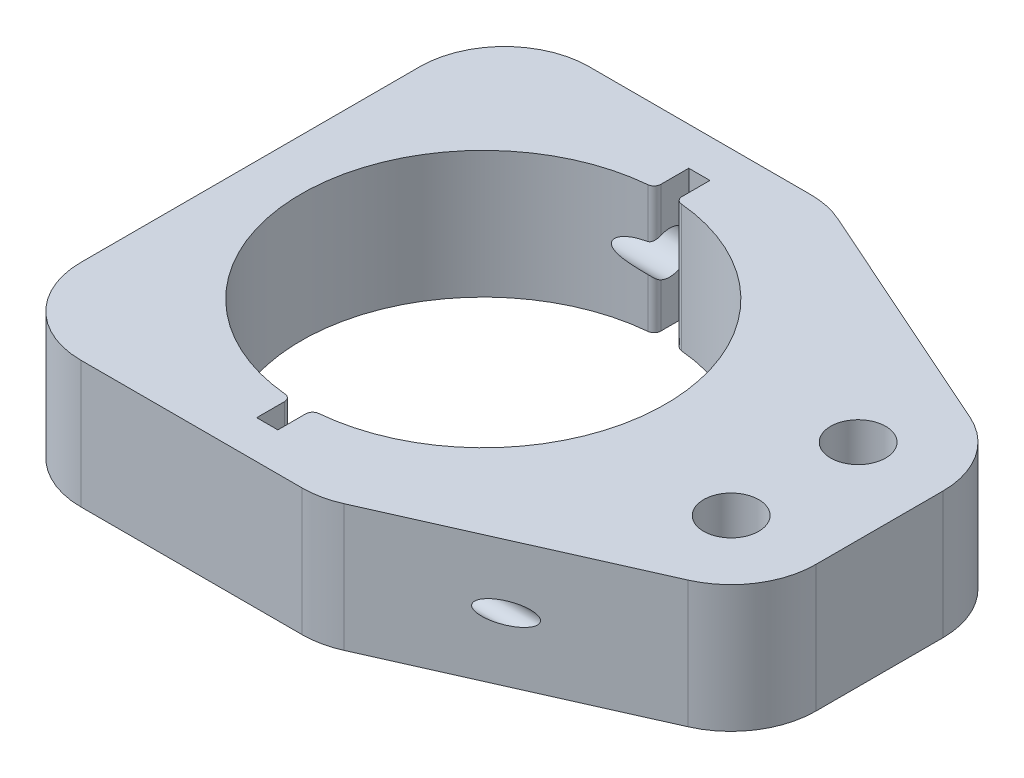
SolidWorks part; units mm, degrees
material "PET"
ref_plane "Front Plane" through (0, 0, 0) normal (0, 0, 1) x (1, 0, 0)
ref_plane "Top Plane" through (0, 0, 0) normal (0, 1, 0) x (1, 0, 0)
ref_plane "Right Plane" through (0, 0, 0) normal (1, 0, 0) x (0, 0, -1)
sketch "Sketch1" plane through (0, 0, 0) normal (0, 1, 0) x (1, 0, 0)
  line L0 (0, 0) -> (-27.5, 0) construction
  line L1 (46.75, 30) -> (-27.5, 30)
  line L2 (46.75, 30) -> (46.75, -30)
  line L3 (46.75, -30) -> (-27.5, -30)
  line L4 (-27.5, 30) -> (-27.5, -30)
  line L5 (-1.25, 21.4636) -> (-1.25, 25.5)
  line L6 (1.25, -25.5) -> (-1.25, -25.5)
  line L7 (1.25, -25.5) -> (1.25, -21.4636)
  line L8 (1.25, 25.5) -> (-1.25, 25.5)
  line L9 (-1.25, -25.5) -> (-1.25, -21.4636)
  line L10 (1.25, -25.5) -> (-1.25, 25.5) construction
  line L11 (1.25, 25.5) -> (-1.25, -25.5) construction
  line L12 (1.25, 21.4636) -> (1.25, 25.5)
  line L13 (36.75, -7.493) -> (36.75, 7.493) construction
  line L14 (36.75, 0) -> (46.75, 0) construction
  arc A0 (-1.25, 21.4636) -> (-1.25, -21.4636) centre (0, 0) ccw
  arc A1 (1.25, -21.4636) -> (1.25, 21.4636) centre (0, 0) ccw
  circle A2 centre (36.75, 7.493) radius 3.25
  circle A3 centre (36.75, -7.493) radius 3.25
  point P7 (-21.5, 0)
  point P10 (-27.5, 0)
  point P23 (21.5, 0)
  point P24 (33.5, 7.493)
  dimension "D1" = 43
  dimension "D6" = 6.5
  dimension "D2" = 6
  dimension "D3" = 60
  dimension "D4" = 51
  dimension "D5" = 2.5
  dimension "D7" = 14.986
  dimension "D8" = 10
  dimension "D9" = 12
extrude "Boss-Extrude1" add sketch "Sketch1" along normal blind 15
sketch "Sketch2" plane through (-27.5, 0, 0) normal (-1, 0, 0) x (0, 0, 1)
  line L0 (-23.25, 7.5) -> (23.25, 7.5) construction
  line L1 (0, 7.5) -> (0, 0) construction
  line L2 (0, 7.5) -> (0, 15) construction
  line L3 (-30, 15) -> (30, 15) construction
  circle A0 centre (-23.25, 7.5) radius 1.25
  circle A1 centre (23.25, 7.5) radius 1.25
  dimension "D1" = 2.5
  dimension "D2" = 46.5
extrude "Cut-Extrude1" cut sketch "Sketch2" against normal through all
sketch "Sketch3" plane through (-27.5, 0, 0) normal (-1, 0, 0) x (0, 0, 1)
  circle A0 centre (-23.25, 7.5) radius 2.5
  circle A1 centre (23.25, 7.5) radius 2.5
  dimension "D1" = 5
extrude "Cut-Extrude2" cut sketch "Sketch3" against normal up to surface (26.25 mm away) up to face at (-1.25, 7.5, -24.5)
sketch "Sketch4" plane through (0, 15, 0) normal (0, 1, 0) x (1, 0, 0)
  line L0 (10.75, -30) -> (46.75, -14)
  line L1 (-27.5, -30) -> (46.75, -30) construction
  line L2 (46.75, -30) -> (46.75, 30) construction
  line L3 (46.75, -14) -> (46.75, -30)
  line L4 (46.75, -30) -> (10.75, -30)
  dimension "D1" = 16
  dimension "D2" = 36
extrude "Cut-Extrude3" cut sketch "Sketch4" against normal through all
mirror "Mirror1" about plane through (0, 0, 0) normal (0, 0, 1) of "Cut-Extrude3"
fillet "Fillet1" radius 10 6 edges at (-27.5, 7.5, -30) (-27.5, 7.5, 30) (46.75, 7.5, 14) (46.75, 7.5, -14) (10.75, 7.5, -30) (10.75, 7.5, 30)
fillet "Fillet2" radius 0.8 6 edges at (1.25, 7.5, 21.4636) (-1.25, 2.8755, 21.4636) (-1.25, 12.1245, 21.4636) (-1.25, 12.1245, -21.4636) (-1.25, 2.8755, -21.4636) (1.25, 7.5, -21.4636)
